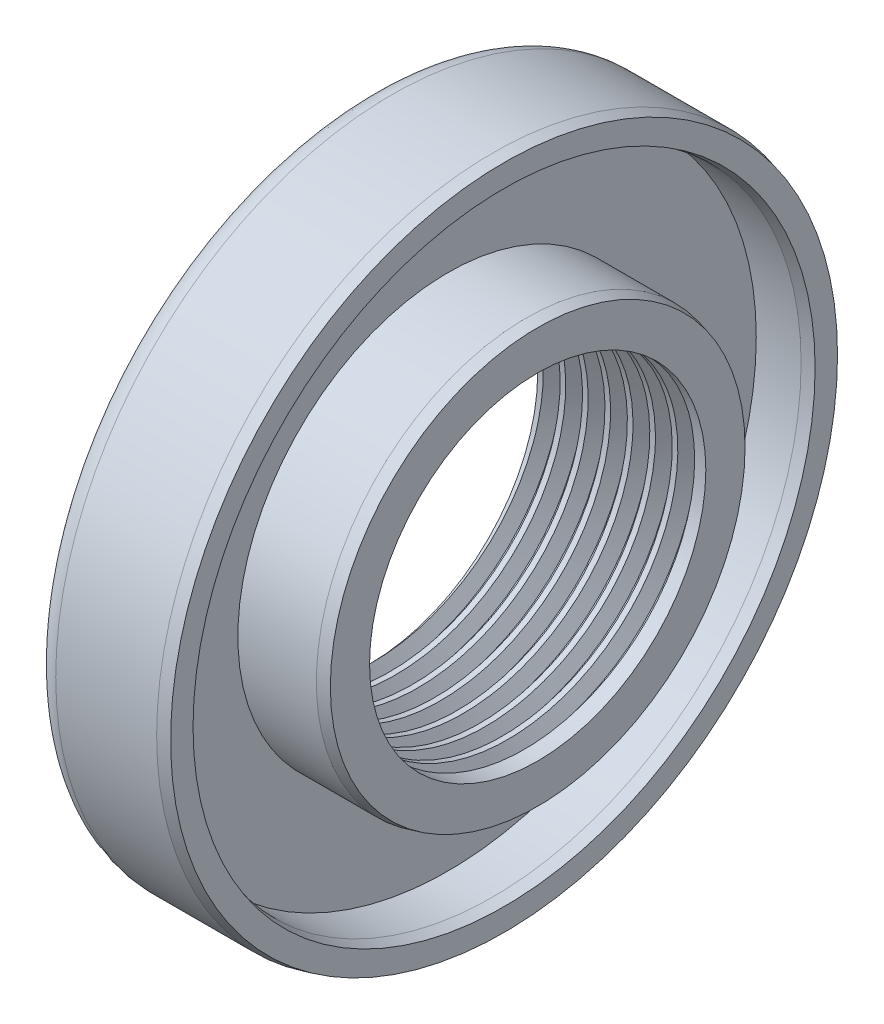
SolidWorks part; units mm, degrees
ref_plane "Front" through (0, 0, 0) normal (0, 0, 1) x (1, 0, 0)
ref_plane "Top" through (0, 0, 0) normal (0, 1, 0) x (1, 0, 0)
ref_plane "Right" through (0, 0, 0) normal (1, 0, 0) x (0, 0, -1)
sketch "Çizim1" plane through (0, 0, 0) normal (0, 0, 1) x (1, 0, 0)
  line L0 (0, 30) -> (-30, 30)
  line L1 (0, 0) -> (-30, 0) construction
  line L2 (0, 0) -> (0, 57.6845) construction
  line L3 (0, 30) -> (0, 37)
  line L4 (-2, 37.5) -> (-16, 37.5)
  line L5 (-16, 37.5) -> (-16, 55)
  line L6 (-16, 55) -> (-8, 55)
  line L8 (-8, 60) -> (-26, 60)
  line L9 (-30, 56) -> (-30, 30)
  line L11 (-6, 59.5) -> (-6, 55.5)
  line L12 (-6, 59.5) -> (-8, 60)
  line L13 (-8, 55) -> (-6, 55.5)
  line L14 (0, 37) -> (-2, 37.5)
  arc A0 (-26, 60) -> (-30, 56) centre (-26, 56) ccw
  point P5 (-16, 30)
  point P7 (0, 37.5)
  point P10 (-6, 55)
  point P11 (-6, 60)
  point P14 (0, 0)
  point P20 (-30, 60)
  dimension "D13" = 4
  dimension "D1" = 30
  dimension "D2" = 2
  dimension "D3" = 30
  dimension "D4" = 37.5
  dimension "D5" = 55
  dimension "D6" = 16
  dimension "D7" = 60
  dimension "D8" = 24
  dimension "D9" = 10
  dimension "D10" = 0.5
  dimension "D11" = 2
  dimension "D12" = 0.5
  dimension "D14" = 2
  dimension "D15" = 0.5
revolve "Döndür1" add sketch "Çizim1" angle 360 about L1
thread "Diş1" pitch 4 method cut profile "Diş Profili2" start angle 0, offset 0, length 50, pitch 4, diameter 60
ref_plane "Düzlem2" through (0, 0, 30) normal (0, -1, 0) x (0, 0, 1)
sketch "Diş Profili2" plane through (0, 0, 30) normal (0, -1, 0) x (0, 0, 1)
  line L0 (0, 0) -> (0, 4) construction
  line L1 (0, 0) -> (2.1651, 1.25)
  line L2 (2.1651, 1.25) -> (2.1651, 1.75)
  line L3 (2.1651, 1.75) -> (0, 3)
  line L4 (2.1651, 1.5) -> (0, 1.5) construction
  line L11 (0, 0) -> (0, 3)
  point P2 (0, 0)
  dimension "Pitch" = 4
  dimension "Profile_Angle" = 60
  dimension "Profile_Land" = 0.5
  dimension "Profile_Height" = 2.1651
